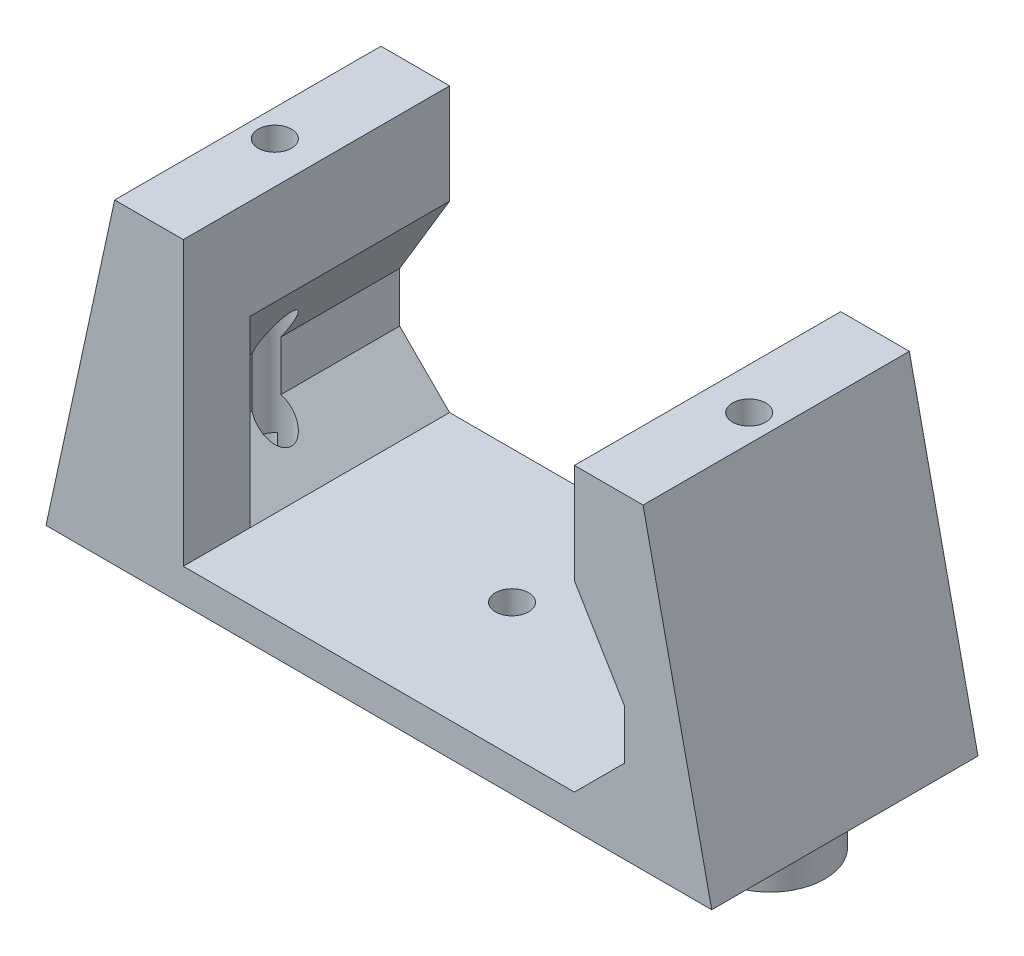
SolidWorks part; units mm, degrees
note: The reader was unsure of these and kept them because the rebuilt part matched: shared geometry of "Esboço1<4>".
ref_plane "Plano frontal" through (0, 0, 0) normal (0, 0, 1) x (1, 0, 0)
ref_plane "Plano superior" through (0, 0, 0) normal (0, 1, 0) x (1, 0, 0)
ref_plane "Plano direito" through (0, 0, 0) normal (1, 0, 0) x (0, 0, -1)
sketch "Esboço1" plane through (0, 0, 0) normal (0, 1, 0) x (1, 0, 0)
  line L0 (0, 0) -> (0, 6.0436) construction
  line L1 (0, 0) -> (15.5, 0) construction
  line L2 (-11.75, 6.75) -> (-11.75, 8)
  line L3 (-11.75, -6.75) -> (11.75, -6.75)
  line L4 (-11.75, -6.75) -> (-11.75, 6.75)
  line L5 (-11.75, 6.75) -> (11.75, 6.75)
  line L6 (11.75, -6.75) -> (11.75, 6.75)
  line L7 (-11.75, -6.75) -> (11.75, 6.75) construction
  line L8 (-11.75, 6.75) -> (11.75, -6.75) construction
  line L9 (-20, -8) -> (20, -8)
  line L10 (-20, -8) -> (-20, 8)
  line L11 (-20, 8) -> (20, 8)
  line L12 (20, -8) -> (20, 8)
  line L13 (-20, -8) -> (20, 8) construction
  line L14 (-20, 8) -> (20, -8) construction
  line L15 (-11.75, 6.75) -> (-16.75, 6.75)
  line L16 (-11.75, 6.75) -> (-11.75, -6.75)
  line L17 (-11.75, -6.75) -> (-16.75, -6.75)
  line L18 (-16.75, 6.75) -> (-16.75, -6.75)
  line L19 (11.75, 6.75) -> (16.75, 6.75)
  line L20 (11.75, 6.75) -> (11.75, -6.75)
  line L21 (11.75, -6.75) -> (16.75, -6.75)
  line L22 (16.75, 6.75) -> (16.75, -6.75)
  line L23 (-11.75, -6.75) -> (-11.75, -8)
  line L24 (11.75, -6.75) -> (11.75, -8)
  line L25 (11.75, 6.75) -> (11.75, 8)
  circle A0 centre (0, 0) radius 3.5
  circle A1 centre (15.5, 0) radius 3.5
  circle A2 centre (-15.5, 0) radius 3.5
  circle A3 centre (-14.25, 0) radius 1
  circle A4 centre (14.25, 0) radius 1
  dimension "D6" = 40
  dimension "D8" = 5
  dimension "D9" = 5
  dimension "D10" = 2
  dimension "D1" = 7
  dimension "D3" = 7
  dimension "D11" = 2
  dimension "D2" = 15.5
  dimension "D4" = 23.5
  dimension "D5" = 13.5
  dimension "D7" = 16
extrude "Ressalto-extrusão1" add sketch "Esboço1" along normal blind 2 contours L3 L6 L5 L4 A0 | L18 A2 L17 L4 L15 | L9 L12 L11 L10 L18 A2 L15 L5 L19 L22 A1 L21 L3 L17 | A1 L22 L19 L6 L21 | A2 L18 A3 | A3 | A2 L18 | A0 | A4 | L22 A1 A4 | L22 A1 | L18 A2 L15 L2 L11 L10 L9 L23 L17 | L5 L25 L11 L2 | A1 L22 L21 L24 L9 L12 L11 L25 L19
extrude "Ressalto-extrusão2" add sketch "Esboço1<4>" along normal blind 19 contours L18 A2 L17 L4 L15 | A2 L18 A3 | A1 L22 L19 L6 L21 | L22 A1 A4 | L18 A2 L15 L2 L11 L10 L9 L23 L17 | A2 L18 | A1 L22 L21 L24 L9 L12 L11 L25 L19 | L22 A1
sketch "Esboço1<4>" plane through (0, 0, 0) normal (0, 1, 0) x (1, 0, 0) same geometry as "Esboço1"
sketch "Esboço2" plane through (0, 0, 0) normal (0, -1, 0) x (1, 0, 0)
  line L0 (15.5, 0) -> (-15.5, 0)
  circle A0 centre (0, 0) radius 3.3
  circle A1 centre (-15.5, 0) radius 3.3
  circle A2 centre (15.5, 0) radius 3.3
  circle A3 centre (-15.5, 0) radius 1
  circle A4 centre (0, 0) radius 1
  circle A5 centre (15.5, 0) radius 1
  point P6 (0, 0)
  dimension "D1" = 6.6
  dimension "D3" = 6.6
  dimension "D4" = 6.6
  dimension "D5" = 2
  dimension "D6" = 2
  dimension "D7" = 2
  dimension "D2" = 31
extrude "Ressalto-extrusão3" add sketch "Esboço2" along normal blind 3
sketch "Esboço3" plane through (0, 0, 8) normal (0, 0, 1) x (1, 0, 0)
  line L0 (0, 0) -> (0, 12.3896) construction
  line L1 (-15.875, 19) -> (-20, 0)
  line L2 (20, 0) -> (15.875, 19)
  line L9 (-20, 0) -> (20, 0)
  line L10 (20, 0) -> (20, 19)
  line L11 (20, 19) -> (11.75, 19)
  line L12 (11.75, 19) -> (11.75, 2)
  line L13 (11.75, 2) -> (-11.75, 2)
  line L14 (-11.75, 2) -> (-11.75, 19)
  line L15 (-11.75, 19) -> (-20, 19)
  line L16 (-20, 19) -> (-20, 0)
  line L17 (-20, 0) -> (20, 0)
  line L18 (20, 0) -> (20, 19)
  line L19 (20, 19) -> (11.75, 19)
  line L20 (11.75, 19) -> (11.75, 2)
  line L21 (11.75, 2) -> (-11.75, 2)
  line L22 (-11.75, 2) -> (-11.75, 19)
  line L23 (-11.75, 19) -> (-20, 19)
  line L24 (-20, 19) -> (-20, 0)
  line M10 (20, 0) -> (20, 19)
  line M11 (20, 19) -> (11.75, 19)
  line M15 (-11.75, 19) -> (-20, 19)
  line M16 (-20, 19) -> (-20, 0)
  dimension "D1" = 0
extrude "Corte-extrusão1" cut sketch "Esboço3" against normal through all contours L2 M10 M11 | L1 M15 M16
sketch "Esboço4" plane through (0, 0, -8) normal (0, 0, -1) x (-1, 0, 0)
  line L0 (11.75, 13) -> (14.75, 8)
  line L1 (11.75, 2) -> (14.75, 2)
  line L2 (11.75, 2) -> (11.75, 5)
  line L3 (11.75, 5) -> (14.75, 5)
  line L4 (14.75, 2) -> (14.75, 5)
  line L5 (14.75, 5) -> (11.75, 5)
  line L6 (14.75, 5) -> (14.75, 13)
  line L7 (14.75, 13) -> (11.75, 13)
  line L8 (-20, 0) -> (20, 0)
  line L9 (20, 0) -> (15.875, 19)
  line L10 (15.875, 19) -> (11.75, 19)
  line L11 (11.75, 19) -> (11.75, 2)
  line L12 (11.75, 2) -> (-11.75, 2)
  line L13 (-11.75, 2) -> (-11.75, 19)
  line L14 (-11.75, 19) -> (-15.875, 19)
  line L15 (-15.875, 19) -> (-20, 0)
  line L16 (-20, 0) -> (20, 0)
  line L17 (20, 0) -> (15.875, 19)
  line L18 (15.875, 19) -> (11.75, 19)
  line L19 (11.75, 19) -> (11.75, 2)
  line L20 (11.75, 2) -> (-11.75, 2)
  line L21 (-11.75, 2) -> (-11.75, 19)
  line L22 (-11.75, 19) -> (-15.875, 19)
  line L23 (-15.875, 19) -> (-20, 0)
  line L24 (11.75, 5) -> (11.75, 13)
  line L25 (13.625, 8) -> (14.75, 5)
  line L27 (14.75, 5) -> (11.75, 5)
  line L28 (14.75, 5) -> (14.75, 8)
  line L29 (14.75, 8) -> (11.75, 8)
  line L30 (11.75, 5) -> (11.75, 8)
  line M15 (11.75, 19) -> (11.75, 2)
  dimension "D2" = 3
  dimension "D3" = 3
  dimension "D4" = 8
  dimension "D5" = 3
  dimension "D1" = 0
extrude "Corte-extrusão3" cut sketch "Esboço4" against normal blind 12 contours L25 L3 M15 | L6 L29 L25 | L29 L0 M15
ref_plane "Plano1" through (-0.25, 0, 0) normal (1, 0, 0) x (0, 0, -1)
sketch "Esboço6" plane through (0, 0, 8) normal (0, 0, 1) x (1, 0, 0)
  line L0 (11.75, 13) -> (14.75, 8)
  line L1 (11.75, 2) -> (14.75, 2)
  line L2 (11.75, 2) -> (11.75, 5)
  line L3 (11.75, 5) -> (14.75, 5)
  line L4 (14.75, 2) -> (14.75, 5)
  line L5 (14.75, 5) -> (11.75, 5)
  line L6 (14.75, 5) -> (14.75, 13)
  line L7 (14.75, 13) -> (11.75, 13)
  line L8 (-15.875, 19) -> (-20, 0)
  line L9 (-20, 0) -> (20, 0)
  line L10 (20, 0) -> (15.875, 19)
  line L11 (15.875, 19) -> (11.75, 19)
  line L12 (11.75, 19) -> (11.75, 2)
  line L13 (11.75, 2) -> (-11.75, 2)
  line L14 (-11.75, 2) -> (-11.75, 19)
  line L15 (-11.75, 19) -> (-15.875, 19)
  line L16 (-15.875, 19) -> (-20, 0)
  line L17 (-20, 0) -> (20, 0)
  line L18 (20, 0) -> (15.875, 19)
  line L19 (15.875, 19) -> (11.75, 19)
  line L20 (11.75, 19) -> (11.75, 2)
  line L21 (11.75, 2) -> (-11.75, 2)
  line L22 (-11.75, 2) -> (-11.75, 19)
  line L23 (-11.75, 19) -> (-15.875, 19)
  line L24 (11.75, 5) -> (11.75, 13)
  line L25 (14.75, 5) -> (11.75, 5)
  line L26 (14.75, 5) -> (14.75, 8)
  line L27 (14.75, 8) -> (11.75, 8)
  line L28 (11.75, 5) -> (11.75, 8)
  dimension "D2" = 3
  dimension "D3" = 3
  dimension "D4" = 8
  dimension "D5" = 3
  dimension "D1" = 0
extrude "Corte-extrusão4" cut sketch "Esboço6" against normal blind 12
chamfer "Chanfro1" distance 3 angle 45 2 edges at (11.75, 5, 2) (-11.75, 5, -2)
sketch "Esboço7" plane through (0, -3, 0) normal (0, -1, 0) x (1, 0, 0)
  line L0 (16.5, 0) -> (14.5, 0)
  circle A0 centre (-15.5, 0) radius 3.3 construction
  circle A1 centre (0, 0) radius 3.3 construction
  circle A2 centre (15.5, 0) radius 3.3 construction
  circle A3 centre (-15.5, 0) radius 3.3
  circle A4 centre (0, 0) radius 3.3
  circle A5 centre (15.5, 0) radius 3.3
  circle A6 centre (15.5, 0) radius 1 construction
  circle A7 centre (15.5, 0) radius 1
  circle A8 centre (-15.5, 0) radius 1 construction
  circle A9 centre (-15.5, 0) radius 1
  circle A10 centre (0, 0) radius 1
  circle M2 centre (15.5, 0) radius 1
extrude "Corte-extrusão5" cut sketch "Esboço7" against normal blind 6 contours A10 | A9 | L0 M2 | L0 M2
